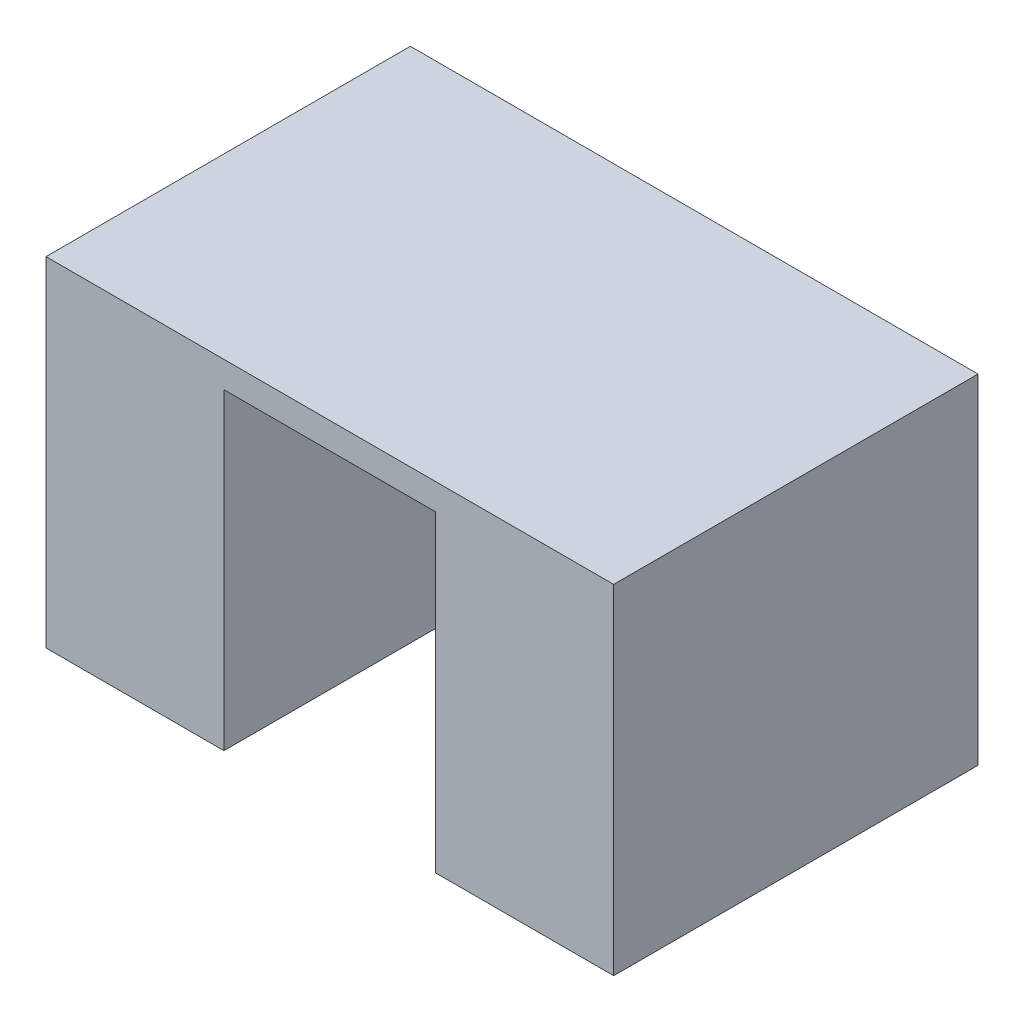
SolidWorks part; units mm, degrees
ref_plane "Front Plane" through (0, 0, 0) normal (0, 0, 1) x (1, 0, 0)
ref_plane "Top Plane" through (0, 0, 0) normal (0, 1, 0) x (1, 0, 0)
ref_plane "Right Plane" through (0, 0, 0) normal (1, 0, 0) x (0, 0, -1)
sketch "Sketch1" plane through (0, 0, 0) normal (0, 1, 0) x (-1, 0, 0)
  line L0 (21, 7.5) -> (21, -35.5)
  line L1 (67, 7.5) -> (0, 7.5)
  line L2 (67, 7.5) -> (67, -35.5)
  line L3 (67, -35.5) -> (0, -35.5)
  line L4 (0, 7.5) -> (0, -35.5)
  line L5 (21, -35.5) -> (46, -35.5)
  line L6 (46, -35.5) -> (46, 7.5)
  line L7 (46, 7.5) -> (21, 7.5)
  dimension "D1" = 43
  dimension "D2" = 67
  dimension "D3" = 25
  dimension "D4" = 21
extrude "Boss-Extrude1" add sketch "Sketch1" along normal blind 40 contours L2 L3 L4 L1
extrude "Cut-Extrude1" cut sketch "Sketch1<3>" along normal blind 36.9 contours L3 L6 L1 L0 region at (-33.5, 0, -14)
sketch "Sketch1<3>" plane through (0, 0, 0) normal (0, 1, 0) x (-1, 0, 0) same geometry as "Sketch1"
